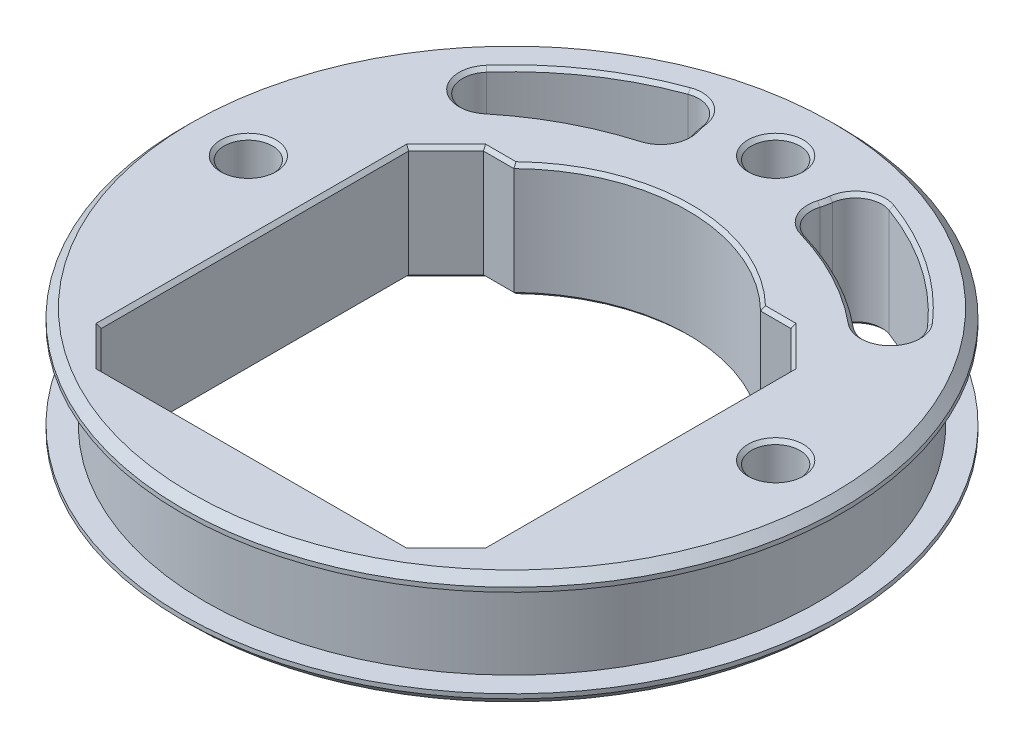
SolidWorks part; units mm, degrees
ref_plane "Front Plane" through (0, 0, 0) normal (0, 0, 1) x (1, 0, 0)
ref_plane "Top Plane" through (0, 0, 0) normal (0, 1, 0) x (1, 0, 0)
ref_plane "Right Plane" through (0, 0, 0) normal (1, 0, 0) x (0, 0, -1)
sketch "Sketch1" plane through (0, 0, 0) normal (0, 1, 0) x (1, 0, 0)
  line L0 (0, 0) -> (0, -7.5) construction
  line L1 (-17.4944, 14.25) -> (-14.0334, 14.25)
  line L2 (17.4944, 14.25) -> (21.75, 9.9944)
  line L3 (21.75, 9.9944) -> (21.75, -24.9944)
  line L4 (21.75, -24.9944) -> (17.4944, -29.25)
  line L5 (17.4944, -29.25) -> (-17.4944, -29.25)
  line L6 (-17.4944, -29.25) -> (-21.75, -24.9944)
  line L7 (-21.75, -24.9944) -> (-21.75, 9.9944)
  line L8 (-21.75, 9.9944) -> (-17.4944, 14.25)
  line L9 (14.0334, 14.25) -> (17.4944, 14.25)
  circle A0 centre (0, 0) radius 35 construction
  circle A1 centre (0, -7.5) radius 27.9127 construction
  circle A2 centre (0, 0) radius 30 construction
  circle A3 centre (0, 30) radius 2.75
  circle A4 centre (30, 0) radius 2.75
  circle A5 centre (-30, 0) radius 2.75
  circle A6 centre (0, 0) radius 37.5
  arc A7 (-20.9311, 17.8995) -> (20.9311, 17.8995) centre (0, -7.5) ccw construction
  arc A8 (7.1823, 27.8402) -> (7.4393, 29.0476) centre (0, 30) ccw
  arc A9 (6.9711, 32.7667) -> (-6.9711, 32.7667) centre (0, 0) ccw construction
  arc A10 (-25.0854, 22.203) -> (-20.9311, 17.8995) centre (-22.8389, 20.2147) ccw
  arc A11 (20.9311, 17.8995) -> (25.0854, 22.203) centre (22.8389, 20.2147) ccw
  arc A12 (-5.5389, 24.9433) -> (5.5389, 24.9433) centre (0, 30) ccw construction
  arc A13 (5.5389, 24.9433) -> (-5.5389, 24.9433) centre (0, -7.5) ccw construction
  arc A14 (-9.2152, 24.0963) -> (-20.9311, 17.8995) centre (0, -7.5) ccw
  arc A15 (20.9311, 17.8995) -> (9.2152, 24.0963) centre (0, -7.5) ccw
  arc A16 (25.0854, 22.203) -> (11.4394, 31.4863) centre (0, 0) ccw
  arc A17 (-11.4394, 31.4863) -> (-25.0854, 22.203) centre (0, 0) ccw
  arc A18 (-25.0854, 22.203) -> (25.0854, 22.203) centre (0, 0) ccw construction
  arc A19 (-7.4393, 29.0476) -> (-7.1823, 27.8402) centre (0, 30) ccw
  arc A20 (6.9711, 32.7667) -> (-6.9711, 32.7667) centre (0, 30) ccw construction
  arc A21 (11.4394, 31.4863) -> (7.4393, 29.0476) centre (10.415, 28.6667) ccw
  arc A22 (7.1823, 27.8402) -> (9.2152, 24.0963) centre (10.0552, 26.9763) ccw
  arc A23 (-9.2152, 24.0963) -> (-7.1823, 27.8402) centre (-10.0552, 26.9763) ccw
  arc A24 (-11.4394, 31.4863) -> (-7.4393, 29.0476) centre (-10.415, 28.6667) cw
  arc A25 (14.0334, 14.25) -> (-14.0334, 14.25) centre (0, 0) ccw
  dimension "D1" = 43.5
  dimension "D2" = 70
  dimension "D5" = 60
  dimension "D6" = 5.5
  dimension "D7" = 2.5
  dimension "D8" = 4
  dimension "D9" = 5
  dimension "D10" = 3
  dimension "D11" = 3
  dimension "D12" = 20
  dimension "D3" = 7.5
  dimension "D4" = 55.5
extrude "Boss-Extrude1" add sketch "Sketch1" along normal mid plane 13
sketch "Sketch2" plane through (0, 0, 0) normal (0, 1, 0) x (1, 0, 0)
  circle A0 centre (0, 0) radius 34.9
  dimension "D1" = 69.8
extrude "Cut-Extrude-Thin1" cut sketch "Sketch2" against normal mid plane 10 thin thin type one direction wall 10
chamfer "Chamfer1" distance 1 angle 45 2 edges at (0, -6.5, 37.5) (0, 6.5, 37.5)
chamfer "Chamfer2" distance 0.4 angle 45 50 edges at (-15.7639, -6.5, -14.25) (0, -6.5, -20) (15.7639, -6.5, -14.25) (19.6222, -6.5, -12.1222) (21.75, -6.5, 7.5) (19.6222, -6.5, 27.1222) (0, -6.5, 29.25) (-19.6222, -6.5, 27.1222) (-21.75, -6.5, 7.5) (-19.6222, -6.5, -12.1222) (30, -6.5, 2.75) (30, 6.5, 2.75) (-30, -6.5, 2.75) (-30, 6.5, 2.75) (0, -6.5, -27.25) (0, 6.5, -27.25) (-15.3883, 6.5, -21.5937) (-7.4188, 6.5, -25.5447) (-24.9973, 6.5, -18.1311) (-7.3357, 6.5, -28.4386) (-18.843, 6.5, -27.6982) (-8.8534, 6.5, -31.2282) (-15.3883, -6.5, -21.5937) (-7.4188, -6.5, -25.5447) (-24.9973, -6.5, -18.1311) (-7.3357, -6.5, -28.4386) (-18.843, -6.5, -27.6982) (-8.8534, -6.5, -31.2282) (7.4188, 6.5, -25.5447) (15.3883, 6.5, -21.5937) (7.3357, 6.5, -28.4386) (24.9973, 6.5, -18.1311) (8.8534, 6.5, -31.2282) (18.843, 6.5, -27.6982) (7.4188, -6.5, -25.5447) (15.3883, -6.5, -21.5937) (7.3357, -6.5, -28.4386) (24.9973, -6.5, -18.1311) (8.8534, -6.5, -31.2282) (18.843, -6.5, -27.6982) (15.7639, 6.5, -14.25) (19.6222, 6.5, -12.1222) (21.75, 6.5, 7.5) (19.6222, 6.5, 27.1222) (0, 6.5, 29.25) (-19.6222, 6.5, 27.1222) (-21.75, 6.5, 7.5) (-19.6222, 6.5, -12.1222) (0, 6.5, -20) (-15.7639, 6.5, -14.25)
